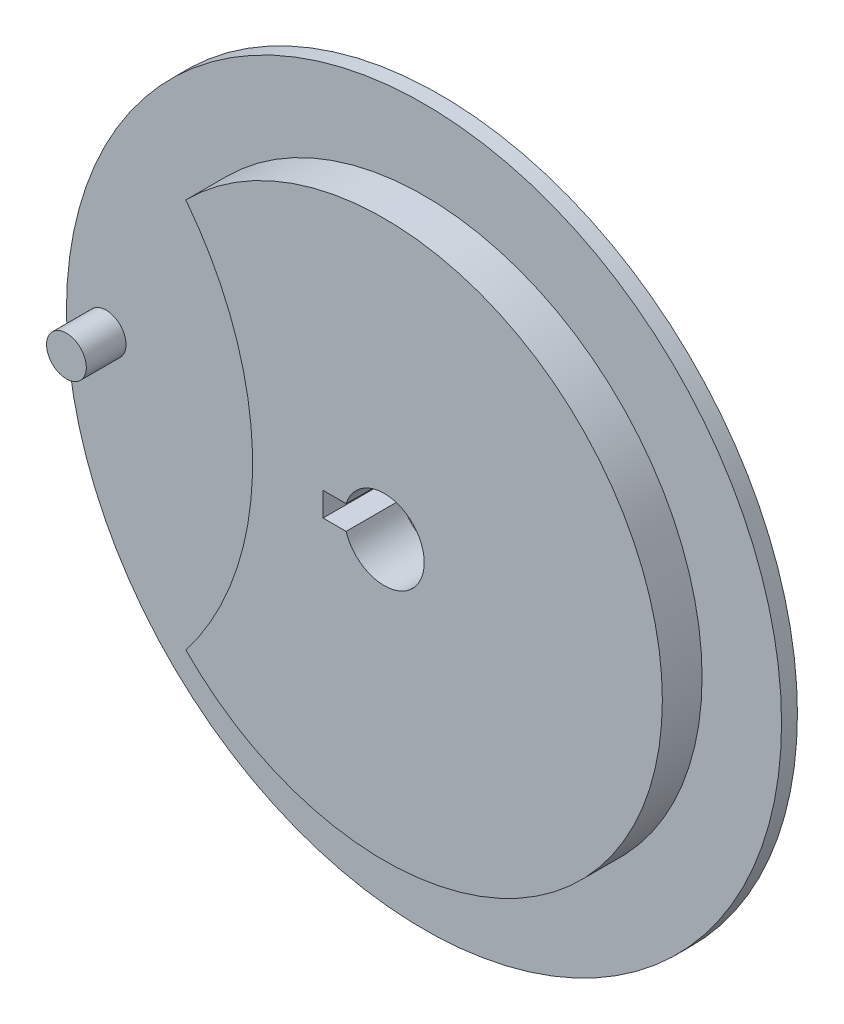
SolidWorks part; units mm, degrees
ref_plane "前视基准面" through (0, 0, 0) normal (0, 0, 1) x (1, 0, 0)
ref_plane "上视基准面" through (0, 0, 0) normal (0, 1, 0) x (1, 0, 0)
ref_plane "右视基准面" through (0, 0, 0) normal (1, 0, 0) x (0, 0, -1)
other "Configuration Table"
sketch "草图1" plane through (0, 0, 0) normal (0, 0, 1) x (1, 0, 0)
  line L0 (-2.5297, 2.5297) -> (-3.6261, 3.6261) construction
  line L1 (0, 0) -> (-1.9675, 1.9675) construction
  circle A0 centre (0, 0) radius 0.1987
  circle A1 centre (0, 0) radius 3.5775
  arc A3 (-1.9851, -1.9498) -> (-1.9851, 1.9498) centre (0, 0) ccw
  circle A4 centre (-3.18, 0) radius 0.1988
  arc A5 (-1.9851, -1.9498) -> (-1.9851, 1.9498) centre (-4.4972, 0) ccw
  dimension "D2" = 0.3975
  dimension "D5" = 0.3975
extrude "凸台-拉伸2" add sketch "草图1" against normal blind 0.159 contours A5 A3 A0 | A1 A4 A3 A5 | A4 region at (-3.4763, 0, 0) region at (0.3939, 0, 0) region at (-3.18, 0, 0)
extrude "凸台-拉伸3" add sketch "草图1<6>" along normal blind 0.3975 contours A5 A3 A0 | A4 region at (0.3939, 0, 0) region at (-3.18, 0, 0)
sketch "草图1<6>" plane through (0, 0, 0) normal (0, 0, 1) x (1, 0, 0) same geometry as "草图1"
scale "缩放比例2" scale about centroid uniform scaling yes scale factor 25
sketch "草图2" plane through (0, 0, 8.1058) normal (0, 0, 1) x (1, 0, 0)
  circle A0 centre (-5.0018, 0) radius 10
  dimension "D1" = 20
extrude "切除-拉伸1" cut sketch "草图2" against normal blind 23
sketch "草图3" plane through (0, 0, 8.1058) normal (0, 0, 1) x (1, 0, 0)
  line L1 (-9.7018, -3) -> (-20.3018, -3)
  line L2 (-9.7018, -3) -> (-9.7018, 3)
  line L3 (-9.7018, 3) -> (-20.3018, 3)
  line L8 (-20.3018, -3) -> (-20.3018, 3)
  line L9 (-9.7018, -3) -> (-20.3018, 3) construction
  line L10 (-9.7018, 3) -> (-20.3018, -3) construction
  circle A1 centre (-5.0018, 0) radius 10 construction
  point P0 (-15.0018, 0)
  dimension "D1" = 6
  dimension "D2" = 10.6
extrude "切除-拉伸2" cut sketch "草图3" against normal blind 40
